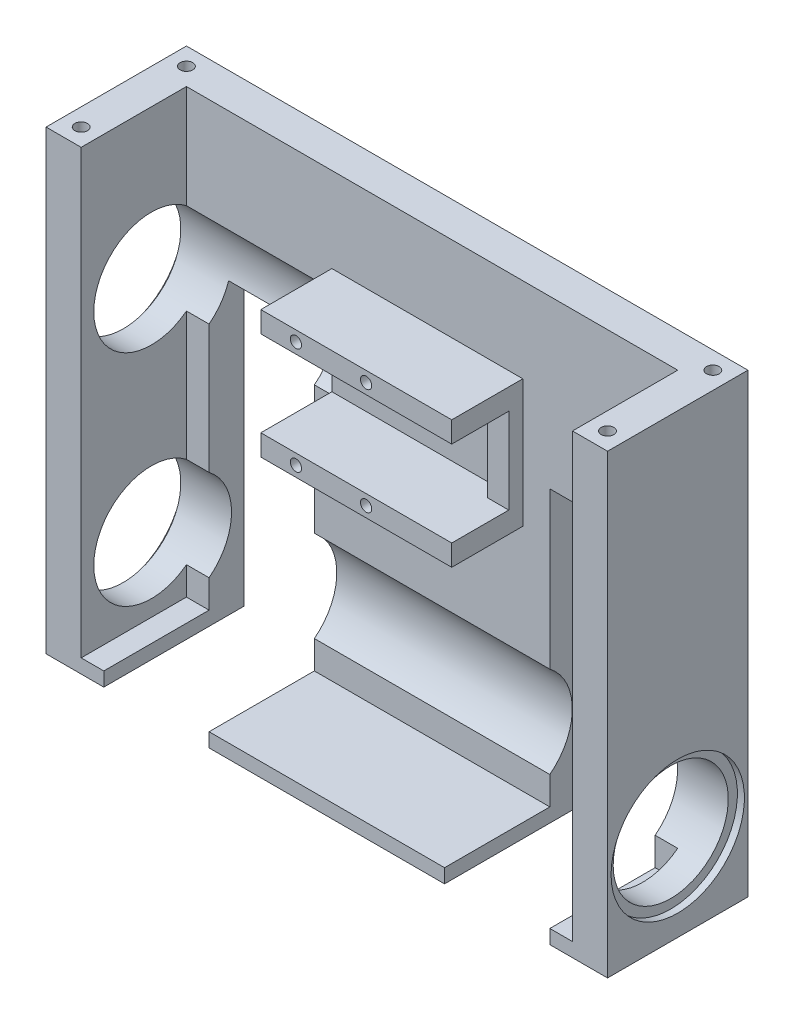
SolidWorks part; units mm, degrees
ref_plane "Front Plane" through (0, 0, 0) normal (0, 0, 1) x (1, 0, 0)
ref_plane "Top Plane" through (0, 0, 0) normal (0, 1, 0) x (1, 0, 0)
ref_plane "Right Plane" through (0, 0, 0) normal (1, 0, 0) x (0, 0, -1)
sketch "Sketch1" plane through (0, 0, 0) normal (0, 0, 1) x (1, 0, 0)
  line L1 (-40, -32.5) -> (40, -32.5)
  line L2 (-40, -32.5) -> (-40, 32.5)
  line L3 (-40, 32.5) -> (40, 32.5)
  line L4 (40, -32.5) -> (40, 32.5)
  line L5 (-40, -32.5) -> (40, 32.5) construction
  line L6 (-40, 32.5) -> (40, -32.5) construction
  point P0 (0, 0)
  dimension "D1" = 80
  dimension "D2" = 65
extrude "Boss-Extrude1" add sketch "Sketch1" along normal blind 20
sketch "Sketch2" plane through (0, 0, 20) normal (0, 0, 1) x (1, 0, 0)
  line L4 (0, 32.5) -> (0, 30.5) construction
  line L7 (40, 32.5) -> (-40, 32.5) construction
  line L8 (0, 30.5) -> (0, -30.5) construction
  line L9 (0, -30.5) -> (0, -32.5) construction
  line L10 (-40, -32.5) -> (40, -32.5) construction
  line L11 (-40, 0) -> (-35, 0) construction
  line L12 (35, -30.5) -> (35, 30.5)
  line L13 (35, 30.5) -> (-35, 30.5)
  line L14 (-35, 30.5) -> (-35, -30.5)
  line L15 (-35, -30.5) -> (35, -30.5)
  line L16 (-40, 32.5) -> (-40, -32.5) construction
  line L17 (-35, 0) -> (35, 0) construction
  line L18 (35, 0) -> (40, 0) construction
  line L19 (40, -32.5) -> (40, 32.5) construction
  dimension "D1" = 5
  dimension "D2" = 2
extrude "Cut-Extrude1" cut sketch "Sketch2" against normal offset from surface (15 mm away) 5 up to face at (0, 0, 0)
sketch "Sketch9" plane through (0, 32.5, 0) normal (0, 1, 0) x (1, 0, 0)
  line L0 (40, -20) -> (-40, -20) construction
  line L1 (-35, -20) -> (35, -20)
  line L2 (-35, -20) -> (-35, -5)
  line L3 (-35, -5) -> (35, -5)
  line L4 (35, -20) -> (35, -5)
  line L5 (-35, -5) -> (35, -5) construction
  line L6 (-35, -5) -> (-35, -20) construction
  line L7 (35, -5) -> (35, -20) construction
extrude "Cut-Extrude7" cut sketch "Sketch9" against normal up to next
sketch "Sketch3" plane through (0, 0, 5) normal (0, 0, 1) x (1, 0, 0)
  line L0 (-14.2764, 20.4) -> (-14.2764, 17.4)
  line L1 (-14.2764, 17.4) -> (9.9236, 17.4)
  line L2 (9.9236, 17.4) -> (9.9236, 5.2)
  line L3 (9.9236, 5.2) -> (-14.2764, 5.2)
  line L4 (-14.2764, 5.2) -> (-14.2764, 2.2)
  line L5 (-14.2764, 2.2) -> (12.9236, 2.2)
  line L6 (12.9236, 2.2) -> (12.9236, 20.4)
  line L7 (12.9236, 20.4) -> (-14.2764, 20.4)
  line L8 (9.9236, 11.3) -> (12.9236, 11.3) construction
  line L9 (9.9236, 17.4) -> (12.9236, 17.4)
  line L10 (9.9236, 5.2) -> (12.9236, 5.2)
  line L11 (8.7629, 11.3) -> (-61.2489, 11.3) construction
  line L12 (-76.2524, -20) -> (48.8109, -20) construction
  point P16 (-53.5366, -20)
  dimension "D1" = 3
  dimension "D2" = 24.2
  dimension "D3" = 12.2
  dimension "D4" = 31.3
  dimension "D5" = 12.5
extrude "Boss-Extrude2" add sketch "Sketch3" along normal blind 10.125 contours L1 L9 L6 L7 L0 | L10 L3 L4 L5 L6 region at (-0.6764, 18.9, 5) region at (-0.6764, 3.7, 5)
extrude "Boss-Extrude3" add sketch "Sketch3<3>" along normal blind 2 contours L2 L8 L6 L9 | L8 L2 L10 L6 region at (11.4236, 14.35, 5) region at (11.4236, 8.25, 5)
sketch "Sketch3<3>" plane through (0, 0, 5) normal (0, 0, 1) x (1, 0, 0) same geometry as "Sketch3"
sketch "Sketch4" plane through (0, 0, 15.125) normal (0, 0, 1) x (1, 0, 0)
  line L0 (-14.2764, 18.9) -> (12.9236, 18.9) construction
  line L1 (-14.2764, 20.4) -> (-14.2764, 17.4) construction
  line L2 (12.9236, 17.4) -> (12.9236, 20.4) construction
  line L3 (-14.2764, 3.7) -> (12.9236, 3.7) construction
  line L4 (-14.2764, 5.2) -> (-14.2764, 2.2) construction
  line L5 (12.9236, 2.2) -> (12.9236, 5.2) construction
  point P12 (-9.2764, 18.9)
  point P13 (0.7236, 18.9)
  point P14 (0.7236, 3.7)
  point P15 (0.7236, 3.7)
  point P16 (-9.2764, 3.7)
  dimension "D1" = 10
  dimension "D2" = 5
hole_wizard "Tap Drill for M2x0.4 Tap1" positions "Sketch5" profile "Sketch6" hole size "M2x0.4" standard "ANSI Metric"
sketch "Sketch5" plane through (0, 0, 15.125) normal (0, 0, 1) x (1, 0, 0)
  point P0 (-9.2764, 18.9)
  point P3 (0.7236, 18.9)
  point P6 (0.7236, 3.7)
  point P9 (0.7236, 3.7)
  point P12 (-9.2764, 3.7)
sketch "Sketch6" plane through (-9.2764, 18.9, 15.125) normal (1, 0, 0) x (0, -1, 0)
  line L0 (0, 0) -> (0, 5.4807)
  line L1 (0, 5.4807) -> (0.8, 5)
  line L2 (0.8, 5) -> (0.8, 0)
  line L5 (0.8, 0) -> (0, 0)
  line L10 (0, 5.4807) -> (-0.8, 5) construction
  line L11 (0, -6.35) -> (0, 107.95) construction
  dimension "Hole Dia." = 1.6
  dimension "Hole Depth" = 5
  dimension "Drill Angle" = 118
sketch "Sketch7" plane through (-40, 0, 0) normal (-1, 0, 0) x (0, 0, 1)
  line L0 (10, -6) -> (10, 39.3037) construction
  line L2 (5, 17.4) -> (5, 5.2) construction
  line L3 (0, 11.3) -> (20, 11.3) construction
  line L4 (0, 32.5) -> (0, -32.5) construction
  line L5 (20, 32.5) -> (20, -32.5) construction
  line L6 (0, -29.6323) -> (25, -29.6323) construction
  circle A0 centre (10, 11.3) radius 8.2
  circle A1 centre (10, 11.3) radius 9.5
  circle A2 centre (10, -20) radius 8.2
  circle A3 centre (10, -20) radius 9.5
  point P6 (5, 11.3)
  point P7 (5, -20)
  point P20 (5, -29.6323)
  dimension "D2" = 16.4
  dimension "D3" = 19
  dimension "D1" = 5
extrude "Cut-Extrude2" cut sketch "Sketch7" against normal up to surface (25.7236 mm away) contours A0 region at (-40, 11.3, 10) up to face at (-14.2764, 18.9, 10.0625)
extrude "Cut-Extrude3" cut sketch "Sketch7<3>" against normal blind 1 contours A1 A0 region at (-40, 11.3, 0.7687)
sketch "Sketch7<3>" plane through (-40, 0, 0) normal (-1, 0, 0) x (0, 0, 1) same geometry as "Sketch7"
extrude "Cut-Extrude4" cut sketch "Sketch7<4>" against normal through all contours A2 region at (-40, -20, 10)
sketch "Sketch7<4>" plane through (-40, 0, 0) normal (-1, 0, 0) x (0, 0, 1) same geometry as "Sketch7"
ref_plane "Plane1" through (0, 0, 0) normal (1, 0, 0) x (0, 0, -1)
extrude "Cut-Extrude5" cut sketch "Sketch7<5>" against normal blind 1 contours A3 A2 region at (-40, -20, 0.7687)
sketch "Sketch7<5>" plane through (-40, 0, 0) normal (-1, 0, 0) x (0, 0, 1) same geometry as "Sketch7"
mirror "Mirror1" about plane through (0, 0, 0) normal (1, 0, 0) of "Cut-Extrude5"
sketch "Sketch8" plane through (0, 0, 0) normal (0, 0, -1) x (-1, 0, 0)
  line L0 (-200008.7629, 11.3) -> (200061.2489, 11.3) construction
  line L1 (29.2764, 1.3) -> (19.2764, 1.3)
  line L2 (29.2764, 1.3) -> (29.2764, 21.3)
  line L3 (29.2764, 21.3) -> (19.2764, 21.3)
  line L4 (19.2764, 1.3) -> (19.2764, 21.3)
  line L5 (29.2764, 1.3) -> (19.2764, 21.3) construction
  line L6 (29.2764, 21.3) -> (19.2764, 1.3) construction
  line L7 (0, 37.5127) -> (0, -50.8434) construction
  line L8 (31.7764, -48.75) -> (16.7764, -48.75)
  line L9 (31.7764, -48.75) -> (31.7764, 8.75)
  line L10 (31.7764, 8.75) -> (16.7764, 8.75)
  line L11 (16.7764, -48.75) -> (16.7764, 8.75)
  line L12 (31.7764, -48.75) -> (16.7764, 8.75) construction
  line L13 (31.7764, 8.75) -> (16.7764, -48.75) construction
  line L14 (-31.7764, -48.75) -> (-16.7764, -48.75)
  line L15 (14.2764, 17.4) -> (14.2764, 5.2) construction
  line L16 (-16.7764, -48.75) -> (-16.7764, 8.75)
  line L17 (200076.2524, -20) -> (-200048.8109, -20) construction
  line L18 (-31.7764, 8.75) -> (-16.7764, 8.75)
  line L19 (-31.7764, -48.75) -> (-31.7764, 8.75)
  line L20 (-24.2764, 8.75) -> (-24.2764, -48.75) construction
  line L21 (24.2764, 8.75) -> (24.2764, -48.75) construction
  point P0 (24.2764, 11.3)
  point P7 (24.2764, -20)
  dimension "D1" = 10
  dimension "D2" = 20
  dimension "D3" = 15
  dimension "D4" = 57.5
  dimension "D5" = 10
extrude "Cut-Extrude6" cut sketch "Sketch8" against normal through all both and the other way through all contours L11 L10 L9 L8 | L16 L18 L19 L14
ref_plane "Plane2" through (24.2764, 0, 0) normal (1, 0, 0) x (0, 0, -1)
ref_plane "Plane3" through (-24.2764, 0, 0) normal (1, 0, 0) x (0, 0, -1)
hole_wizard "Tap Drill for M2x0.4 Tap2" positions "Sketch10" profile "Sketch12" hole size "M2x0.4" standard "ANSI Metric"
sketch "Sketch10" plane through (0, 32.5, 0) normal (0, 1, 0) x (1, 0, 0)
  line L1 (-37.5, -17.5) -> (37.5, -17.5) construction
  line L2 (-37.5, -17.5) -> (-37.5, -2.5) construction
  line L3 (-37.5, -2.5) -> (37.5, -2.5) construction
  line L4 (37.5, -17.5) -> (37.5, -2.5) construction
  line L5 (40, 0) -> (-40, 0) construction
  line L6 (-40, -20) -> (-40, 0) construction
  line L7 (40, -20) -> (40, 0) construction
  line L8 (-35, -20) -> (-40, -20) construction
  point P0 (-37.5, -17.5)
  point P2 (-37.5, -2.5)
  point P4 (37.5, -2.5)
  point P6 (37.5, -17.5)
  dimension "D1" = 2.5
  dimension "D2" = 2.5
  dimension "D3" = 2.5
  dimension "D4" = 2.5
sketch "Sketch12" plane through (-37.5, 32.5, 17.5) normal (1, 0, 0) x (0, 0, 1)
  line L0 (0, 0) -> (0, 10.5408)
  line L1 (0, 10.5408) -> (0.9, 10)
  line L2 (0.9, 10) -> (0.9, 0)
  line L5 (0.9, 0) -> (0, 0)
  line L10 (0, 10.5408) -> (-0.9, 10) construction
  line L11 (0, -6.35) -> (0, 107.95) construction
  dimension "Hole Dia." = 1.8
  dimension "Hole Depth" = 10
  dimension "Drill Angle" = 118
